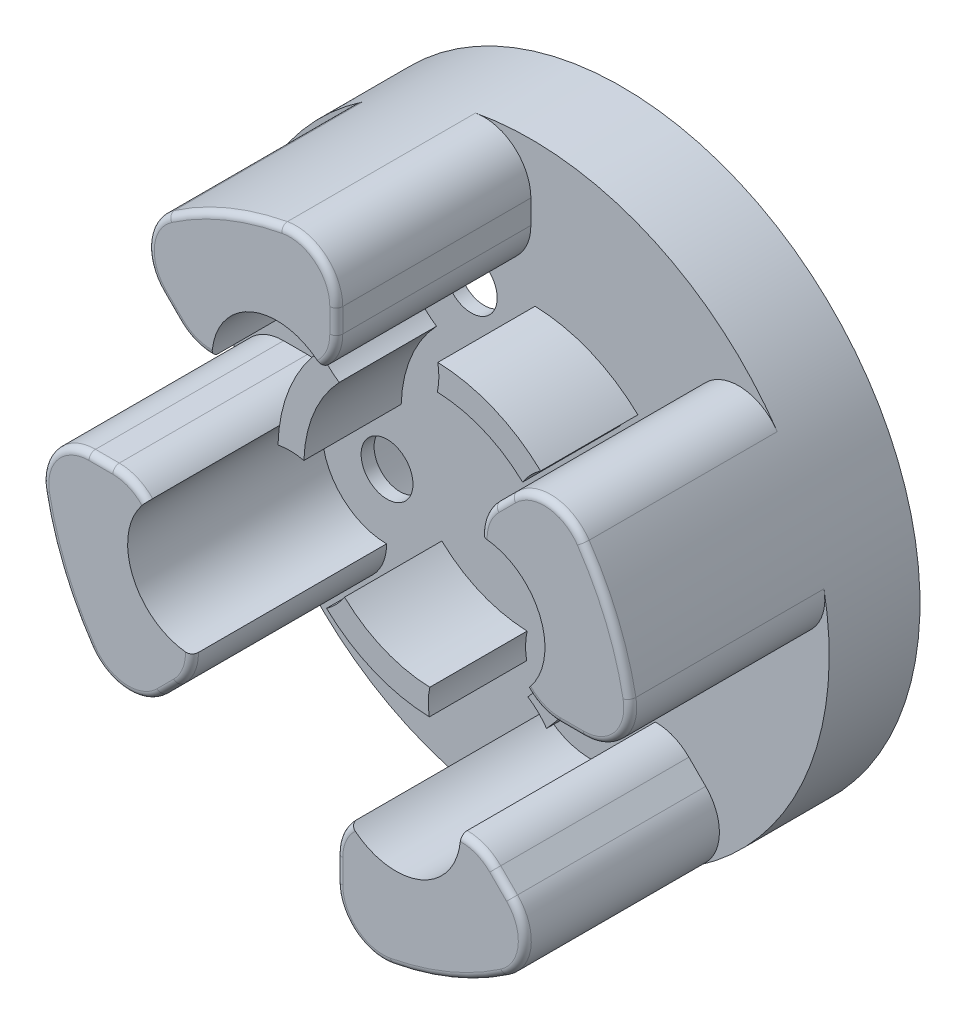
SolidWorks part; units mm, degrees
ref_plane "Front Plane" through (0, 0, 0) normal (0, 0, 1) x (1, 0, 0)
ref_plane "Top Plane" through (0, 0, 0) normal (0, 1, 0) x (1, 0, 0)
ref_plane "Right Plane" through (0, 0, 0) normal (1, 0, 0) x (0, 0, -1)
sketch "Sketch1" plane through (0, 0, 0) normal (0, 0, 1) x (1, 0, 0)
  circle A0 centre (0, 0) radius 11.5
  dimension "D1" = 23
extrude "Boss-Extrude1" add sketch "Sketch1" along normal blind 1
sketch "Sketch3" plane through (0, 0, 1) normal (0, 0, 1) x (1, 0, 0)
  line L0 (0, 11.5) -> (0, 7)
  line L1 (11.5, 0) -> (7, 0)
  line L2 (-8.1317, 8.1317) -> (-4.9497, 4.9497)
  line L3 (4.9497, 4.9497) -> (8.1317, 8.1317)
  line L4 (-4.9497, -4.9497) -> (-8.1317, -8.1317)
  line L5 (0, -7) -> (0, -11.5)
  line L6 (4.9497, -4.9497) -> (8.1317, -8.1317)
  line L7 (-7, 0) -> (-11.5, 0)
  arc A0 (0, 7) -> (-4.9497, 4.9497) centre (0, 0) ccw
  arc A1 (0, 11.5) -> (-8.1317, 8.1317) centre (0, 0) ccw
  arc A2 (-11.5, 0) -> (-8.1317, -8.1317) centre (0, 0) ccw
  arc A3 (-7, 0) -> (-4.9497, -4.9497) centre (0, 0) ccw
  arc A4 (0, -7) -> (4.9497, -4.9497) centre (0, 0) ccw
  arc A5 (0, -11.5) -> (8.1317, -8.1317) centre (0, 0) ccw
  arc A6 (7, 0) -> (4.9497, 4.9497) centre (0, 0) ccw
  arc A7 (11.5, 0) -> (8.1317, 8.1317) centre (0, 0) ccw
  circle A8 centre (0, 0) radius 11.5 construction
  point P11 (0, 0)
  dimension "D1" = 14
  dimension "D5" = 0
  dimension "D2" = 45
  dimension "D3" = 45
  dimension "D4" = 45
extrude "Boss-Extrude2" add sketch "Sketch3" along normal blind 7.5
sketch "Sketch9" plane through (0, 0, 0) normal (0, 0, -1) x (-1, 0, 0)
  circle A0 centre (0, 0) radius 11.5
  dimension "D1" = 23
extrude "Boss-Extrude4" add sketch "Sketch9" along normal blind 2.5
sketch "Sketch10" plane through (0, 0, -2.5) normal (0, 0, -1) x (-1, 0, 0)
  line L0 (0, 0) -> (11.5, 0) construction
  line L1 (3.8766, -9.3589) -> (0, 0) construction
  line L2 (-2.9735, 7.1785) -> (0, 0) construction
  circle A3 centre (-2.9735, 7.1785) radius 1.7
  circle A5 centre (3.8766, -9.3589) radius 1.7
  dimension "D1" = 7.77
  dimension "D2" = 10.13
  dimension "D3" = 3.4
  dimension "D4" = 3.4
  dimension "D5" = 180
  dimension "D6" = 112.5
extrude "Cut-Extrude4" [suppressed] cut sketch "Sketch10" against normal blind 2
fillet "Fillet3" [suppressed] radius 1.5
sketch "Sketch13" [suppressed] plane through (0, 0, -2.5) normal (0, 0, -1) x (-1, 0, 0)
  line L0 (2.1957, -10.2679) -> (-2.1957, -10.2679)
  line L1 (2.1957, -10.2679) -> (2.1957, -15.7368)
  line L2 (-2.1957, -10.2679) -> (-2.1957, -15.7368)
  line L3 (2.1957, -15.7368) -> (-2.1957, -15.7368)
  line L4 (-2.1957, -10.2679) -> (-2.6139, -12.2236) construction
  arc A0 (2.1957, -10.2679) -> (-2.1957, -10.2679) centre (0, -10.13) ccw construction
sketch "Sketch14" [suppressed] plane through (0, 0, -2.5) normal (0, 0, -1) x (-1, 0, 0)
  line L8 (-2.9735, 7.1785) -> (0, 0) construction
  line L9 (0, 0) -> (4.4009, -10.6246) construction
  line L10 (-1.4029, 7.8291) -> (-0.6375, 5.9813)
  line L11 (-0.6375, 5.9813) -> (-3.7787, 4.6802)
  line L12 (-3.7787, 4.6802) -> (-4.544, 6.528)
  line L13 (-1.4029, 7.8291) -> (-4.544, 6.528)
  line L14 (2.306, -10.0095) -> (3.4015, -12.6543)
  line L15 (3.4015, -12.6543) -> (6.5427, -11.3531)
  line L16 (6.5427, -11.3531) -> (5.4472, -8.7083)
  line L17 (5.4472, -8.7083) -> (2.306, -10.0095)
  arc A1 (3.392, -10.9884) -> (5.3714, -10.1685) centre (0, 0) ccw construction
  circle A2 centre (-2.9735, 7.1785) radius 1.7 construction
  arc A3 (2.2222, -9.75) -> (3.392, -10.9884) centre (3.8766, -9.3589) ccw construction
  arc A4 (5.3714, -10.1685) -> (3.392, -10.9884) centre (3.8766, -9.3589) ccw construction
  arc A5 (5.3714, -10.1685) -> (5.323, -8.4656) centre (3.8766, -9.3589) ccw construction
  dimension "D1" = 90
  dimension "D2" = 90
  dimension "D3" = 2
  dimension "D4" = 90
  dimension "D5" = 90
  dimension "D6" = 0
extrude "Cut-Extrude6" [suppressed] cut sketch "Sketch14" against normal blind 2
fillet "Fillet4" [suppressed] radius 0.25
fillet "Fillet6" [suppressed] radius 1.8
fillet "Fillet7" radius 1.8 16 edges at (-11.5, 0, 4.75) (-8.1317, -8.1317, 4.75) (-4.9497, -4.9497, 4.75) (-7, 0, 4.75) (0, -11.5, 4.75) (0, -7, 4.75) (7, 0, 4.75) (11.5, 0, 4.75) (0, 7, 4.75) (-8.1317, 8.1317, 4.75) (8.1317, -8.1317, 4.75) (4.9497, -4.9497, 4.75) (4.9497, 4.9497, 4.75) (8.1317, 8.1317, 4.75) (-4.9497, 4.9497, 4.75) (0, 11.5, 4.75)
sketch "Sketch15" plane through (0, 0, -2.5) normal (0, 0, -1) x (-1, 0, 0)
  circle A0 centre (0, 0) radius 8.025
  dimension "D1" = 16.05
extrude "Cut-Extrude7" cut sketch "Sketch15" against normal blind 3
sketch "Sketch16" plane through (0, 0, 0.5) normal (0, 0, -1) x (-1, 0, 0)
  circle A0 centre (0, 6) radius 0.75
  circle A1 centre (6, 0) radius 0.75
  circle A2 centre (-6, 0) radius 0.75
  circle A3 centre (0, -6) radius 0.75
  dimension "D1" = 1.5
  dimension "D2" = 1.5
  dimension "D3" = 1.5
  dimension "D4" = 1.5
  dimension "D5" = 6
  dimension "D6" = 6
  dimension "D8" = 6
  dimension "D7" = 6
extrude "Boss-Extrude6" [suppressed] add sketch "Sketch16" along normal blind 3
sketch "Sketch17" plane through (0, 0, 1) normal (0, 0, 1) x (1, 0, 0)
  circle A0 centre (0, 0) radius 6
  circle A1 centre (0, 0) radius 5
  dimension "D1" = 12
  dimension "D2" = 10
extrude "Boss-Extrude7" add sketch "Sketch17" along normal blind 3.75
fillet "Fillet8" radius 0.25 32 edges at (-5.5733, -5.0033, 8.5) (-6.4154, -6.4154, 8.5) (-8.1803, -7.2592, 8.5) (-10.6246, -4.4009, 8.5) (-10.9174, -0.6514, 8.5) (-9.0727, 0, 8.5) (-7.4788, -0.4031, 8.5) (-6.4672, -2.6788, 8.5) (5.0033, -5.5733, 8.5) (6.4154, -6.4154, 8.5) (7.2592, -8.1803, 8.5) (4.4009, -10.6246, 8.5) (0.6514, -10.9174, 8.5) (0, -9.0727, 8.5) (0.4031, -7.4788, 8.5) (2.6788, -6.4672, 8.5) (7.4788, 0.4031, 8.5) (6.4672, 2.6788, 8.5) (5.5733, 5.0033, 8.5) (6.4154, 6.4154, 8.5) (8.1803, 7.2592, 8.5) (10.6246, 4.4009, 8.5) (10.9174, 0.6514, 8.5) (9.0727, 0, 8.5) (-5.0033, 5.5733, 8.5) (-6.4154, 6.4154, 8.5) (-7.2592, 8.1803, 8.5) (-4.4009, 10.6246, 8.5) (-0.6514, 10.9174, 8.5) (0, 9.0727, 8.5) (-0.4031, 7.4788, 8.5) (-2.6788, 6.4672, 8.5)
fillet "Fillet9" [suppressed] radius 1.8
sketch "Sketch18" [suppressed] plane through (0, 0, 1) normal (0, 0, 1) x (1, 0, 0)
  circle A0 centre (0, 0) radius 5
  circle A1 centre (0, 0) radius 6
  dimension "D1" = 10
  dimension "D2" = 12
extrude "Boss-Extrude8" [suppressed] add sketch "Sketch18" along normal blind 3.75
sketch "Sketch20" [suppressed] plane through (0, 0, 8.5) normal (0, 0, 1) x (1, 0, 0)
  circle A0 centre (0, 0) radius 11.5
  circle A1 centre (0, 0) radius 14.25
  dimension "D1" = 23
extrude "Cut-Extrude8" [suppressed] cut sketch "Sketch20" against normal blind 2
fillet "Fillet11" [suppressed] radius 1.2
fillet "Fillet12" [suppressed] radius 1.8
sketch "Sketch21" plane through (0, 0, 1) normal (0, 0, 1) x (1, 0, 0)
  line L0 (0, 0) -> (-4.3052, 10.3936) construction
  arc A0 (-2.0876, 11.0546) -> (-6.3406, 9.293) centre (0, 0) ccw construction
  circle A1 centre (-2.2961, 5.5433) radius 2.5
  circle A2 centre (0, 0) radius 6 construction
  dimension "D1" = 6
extrude "Cut-Extrude9" cut sketch "Sketch21" along normal blind 10
sketch "Sketch22" plane through (0, 0, 1) normal (0, 0, 1) x (1, 0, 0)
  circle A0 centre (-2.2961, 5.5433) radius 1
  dimension "D1" = 2
extrude "Cut-Extrude10" cut sketch "Sketch22" against normal blind 10
sketch "Sketch23" [suppressed] plane through (0, 0, -2.5) normal (0, 0, -1) x (-1, 0, 0)
  line L0 (0, 0) -> (0, 6) construction
  line L1 (0, 0) -> (2.2961, 5.5433) construction
pattern_circular "CirPattern5" count 4 every 90 about axis through (0, 0, 1) along (0, 0, 1) of "Cut-Extrude9"
pattern_circular "CirPattern6" count 4 every 90 about axis through (0, 0, 1) along (0, 0, 1) of "Cut-Extrude10"
